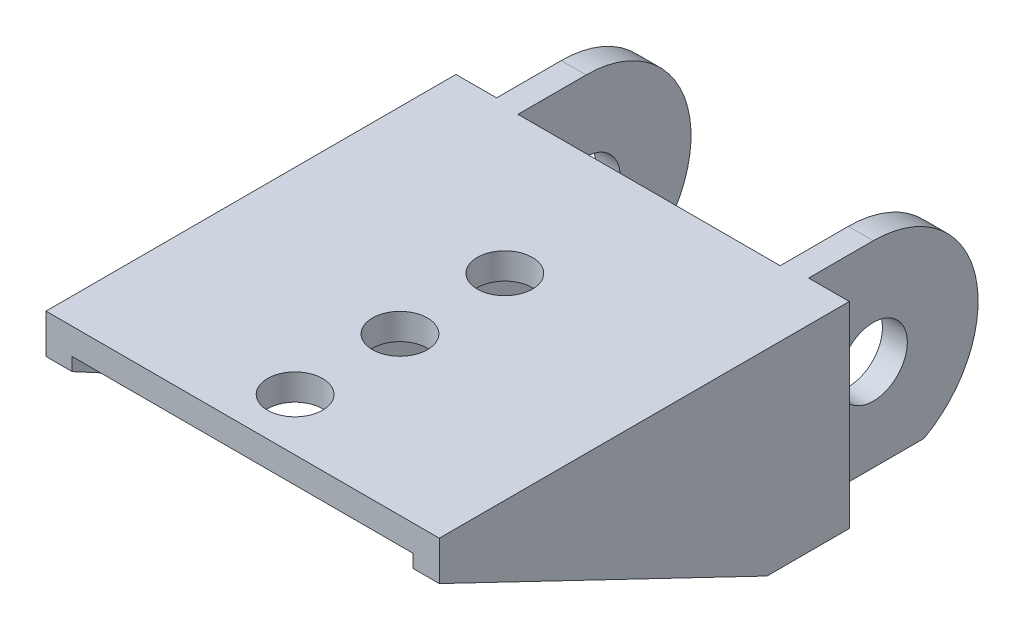
SolidWorks part; units mm, degrees
ref_plane "前基準面" through (0, 0, 0) normal (0, 0, 1) x (1, 0, 0)
ref_plane "上基準面" through (0, 0, 0) normal (0, 1, 0) x (1, 0, 0)
ref_plane "右基準面" through (0, 0, 0) normal (1, 0, 0) x (0, 0, -1)
sketch "草圖1" plane through (0, 0, 0) normal (0, 0, 1) x (1, 0, 0)
  line L1 (-12.751, 5.0503) -> (17.249, 5.0503)
  line L2 (-12.751, 5.0503) -> (-12.751, -9.9497)
  line L3 (-12.751, -9.9497) -> (17.249, -9.9497)
  line L4 (17.249, 5.0503) -> (17.249, -9.9497)
  dimension "D1" = 30
  dimension "D2" = 15
extrude "填料-伸長1" add sketch "草圖1" along normal blind 18
sketch "草圖2" plane through (0, 0, 18) normal (0, 0, 1) x (1, 0, 0)
  line L0 (-12.751, 5.0503) -> (-12.751, -9.9497) construction
  line L1 (-7.751, 3.0503) -> (12.249, 3.0503)
  line L2 (-7.751, 3.0503) -> (-7.751, -6.9497)
  line L3 (-7.751, -6.9497) -> (12.249, -6.9497)
  line L4 (12.249, 3.0503) -> (12.249, -6.9497)
  line L5 (17.249, -9.9497) -> (17.249, 5.0503) construction
  line L6 (17.249, 5.0503) -> (-12.751, 5.0503) construction
  line L7 (-12.751, -9.9497) -> (17.249, -9.9497) construction
  dimension "D1" = 5
  dimension "D2" = 5
  dimension "D3" = 2
  dimension "D4" = 3
extrude "除料-伸長1" cut sketch "草圖2" against normal up to next
sketch "草圖3" plane through (0, -6.9497, 0) normal (0, 1, 0) x (1, 0, 0)
  line L0 (-7.751, 0) -> (-7.751, -18) construction
  line L1 (-7.751, -6) -> (12.249, -6)
  line L2 (-7.751, -6) -> (-7.751, -18)
  line L3 (-7.751, -18) -> (12.249, -18)
  line L4 (12.249, -6) -> (12.249, -18)
  dimension "D1" = 12
extrude "除料-伸長2" cut sketch "草圖3" against normal up to next
sketch "草圖9" plane through (0, 0, 0) normal (0, 0, -1) x (-1, 0, 0)
  line L0 (-17.249, 5.0503) -> (12.751, 5.0503) construction
  line L1 (-12.249, 5.0503) -> (7.751, 5.0503)
  line L2 (-12.249, 5.0503) -> (-12.249, -9.9497)
  line L3 (-12.249, -9.9497) -> (7.751, -9.9497)
  line L4 (7.751, 5.0503) -> (7.751, -9.9497)
  line L5 (12.751, -9.9497) -> (-17.249, -9.9497) construction
  line L6 (-12.249, 3.0503) -> (-12.249, -6.9497) construction
  line L7 (9.651, -9.9497) -> (-14.149, -9.9497)
  line L8 (9.651, -9.9497) -> (9.651, 5.0503)
  line L9 (9.651, 5.0503) -> (-14.149, 5.0503)
  line L10 (-14.149, -9.9497) -> (-14.149, 5.0503)
  line L11 (7.751, -6.9497) -> (7.751, 3.0503) construction
  line M6 (7.751, 3.0503) -> (7.751, -6.9497)
  line M8 (-12.249, -6.9497) -> (-12.249, 3.0503)
  line M10 (12.751, 5.0503) -> (-17.249, 5.0503)
  line M12 (-17.249, -9.9497) -> (12.751, -9.9497)
  dimension "D1" = 1.9
  dimension "D2" = 1.9
extrude "填料-伸長4" add sketch "草圖9" along normal blind 20 contours L8 L4 M12 M10 M6 | L10 L2 M12 M8 M10 region at (13.199, -2.4497, 0) region at (-8.701, -2.4497, 0)
sketch "草圖10" plane through (14.149, 0, 0) normal (1, 0, 0) x (0, 0, -1)
  line L0 (0, -9.9497) -> (0, 5.0503) construction
  line L1 (20, -9.9497) -> (0, -9.9497) construction
  circle A0 centre (5.2, -2.9497) radius 2.6
  dimension "D1" = 5.2
  dimension "D2" = 5.2
  dimension "D3" = 7
extrude "除料-伸長8" cut sketch "草圖10" against normal through all
sketch "草圖12" plane through (14.149, 0, 0) normal (1, 0, 0) x (0, 0, -1)
  line L1 (5.2, 5.0503) -> (18.304, 5.0503)
  line L2 (5.2, 5.0503) -> (5.2, -15.4926)
  line L3 (5.2, -15.4926) -> (18.304, -15.4926)
  line L4 (18.304, 5.0503) -> (18.304, -15.4926)
  circle A0 centre (5.2, -2.9497) radius 8
  line M3 (0, -9.9497) -> (20, -9.9497)
  line M4 (20, -9.9497) -> (20, 5.0503)
  line M5 (20, 5.0503) -> (0, 5.0503)
extrude "除料-伸長9" cut sketch "草圖12" against normal through all both and the other way through all contours A0 L4 M3 M5 | L4 M5 M3 M4 region at (14.149, -2.1497, -14.8341) region at (14.149, -2.4497, -19.152)
sketch "草圖17" plane through (0, 0, 0) normal (0, 0, -1) x (-1, 0, 0)
  line L1 (-17.249, 5.0503) -> (-14.149, 5.0503)
  line L2 (-17.249, 5.0503) -> (-17.249, -9.9497)
  line L3 (-17.249, -9.9497) -> (-14.149, -9.9497)
  line L4 (-14.149, 5.0503) -> (-14.149, -9.9497)
  line L5 (9.651, 5.0503) -> (12.751, 5.0503)
  line L6 (9.651, 5.0503) -> (9.651, -9.9497)
  line L7 (9.651, -9.9497) -> (12.751, -9.9497)
  line L8 (12.751, 5.0503) -> (12.751, -9.9497)
extrude "填料-伸長8" add sketch "草圖17" along normal blind 0.27
sketch "草圖18" plane through (0, 0, 18) normal (0, 0, 1) x (1, 0, 0)
  line L0 (-12.751, 5.0503) -> (-12.751, -9.9497)
  line L1 (-12.751, -9.9497) -> (-7.751, -9.9497)
  line L2 (-7.751, -9.9497) -> (-7.751, 3.0503)
  line L3 (-7.751, 3.0503) -> (12.249, 3.0503)
  line L4 (12.249, 3.0503) -> (12.249, -9.9497)
  line L5 (12.249, -9.9497) -> (17.249, -9.9497)
  line L6 (17.249, -9.9497) -> (17.249, 5.0503)
  line L7 (17.249, 5.0503) -> (-12.751, 5.0503)
extrude "填料-伸長9" add sketch "草圖18" along normal blind 13
chamfer "導角1" distance 25 distance2 12 2 edges at (14.749, -9.9497, 31) (-10.251, -9.9497, 31) first distance on face at (2.249, -9.9497, 6.1643)
sketch "草圖19" plane through (0, 3.0503, 0) normal (0, -1, 0) x (-1, 0, 0)
  line L1 (7.751, 0) -> (7.751, -31) construction
  line L2 (7.751, -31) -> (-12.249, -31) construction
  circle A0 centre (-2.249, -27) radius 2.1
  circle A1 centre (-2.249, -19) radius 2.1
  circle A2 centre (-2.249, -11) radius 2.1
  dimension "D1" = 10
  dimension "D2" = 4.2
  dimension "D3" = 4
  dimension "D4" = 3
extrude "除料-伸長10" cut sketch "草圖19" against normal blind 13
chamfer "導角2" distance 25 distance2 3 2 edges at (12.249, 2.5503, 31) (-7.751, 2.5503, 31) first distance on face at (12.249, -0.3497, -5.2) first distance on face at (-7.751, -5.5497, -5.2)
